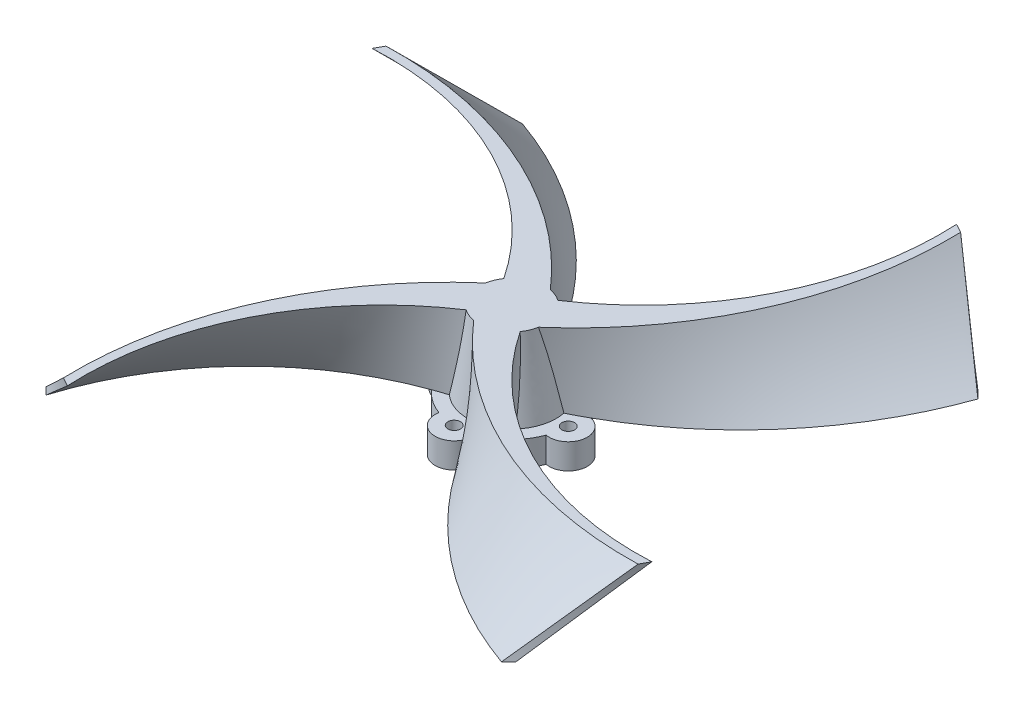
SolidWorks part; units mm, degrees
ref_plane "Front Plane" through (0, 0, 0) normal (0, 0, 1) x (1, 0, 0)
ref_plane "Top Plane" through (0, 0, 0) normal (0, 1, 0) x (1, 0, 0)
ref_plane "Right Plane" through (0, 0, 0) normal (1, 0, 0) x (0, 0, -1)
sketch "Sketch1" plane through (0, 0, 0) normal (0, 1, 0) x (1, 0, 0)
  circle A0 centre (0, 0) radius 22.5
  circle A1 centre (-22.4978, 0.3133) radius 2.5
  circle A2 centre (-22.4978, 0.3133) radius 7.5
  circle A3 centre (0.3133, 22.4978) radius 7.5
  circle A4 centre (0.3133, 22.4978) radius 2.5
  circle A5 centre (22.4978, -0.3133) radius 7.5
  circle A6 centre (22.4978, -0.3133) radius 2.5
  circle A7 centre (-0.3133, -22.4978) radius 7.5
  circle A8 centre (-0.3133, -22.4978) radius 2.5
  point P18 (0, 0)
  point P23 (0, 0)
  dimension "D1" = 45
  dimension "D2" = 15
  dimension "D3" = 5
  dimension "D5" = 4
  dimension "D6" = 22.4978
  dimension "D7" = 31.8198
  dimension "D4" = 22.4978
extrude "Boss-Extrude1" add sketch "Sketch1" along normal blind 10 contours A7 A0 A5 A3 A2 | A4 A0 A3 | A4 A0 A3 | A6 A0 A5 | A6 A0 A5 | A8 A0 A7 | A8 A0 A7 | A0 A2 A1 | A0 A2 A1 region at (18.7951, 0, 0.2617) region at (25.672, 0, 0.3574) region at (0, 0, 0) region at (0.2617, 0, -18.7951) region at (0.3574, 0, -25.672) region at (-0.3574, 0, 25.672) region at (-0.2617, 0, 18.7951) region at (-18.7951, 0, -0.2617) region at (-25.672, 0, -0.3574)
ref_plane "Plane1" through (0, 40, 0) normal (0, 1, 0) x (1, 0, 0)
sketch "Sketch11" plane through (0, 10, 0) normal (0, 1, 0) x (1, 0, 0)
  arc A1 (93.9749, 89.826) -> (91.1669, 92.6747) centre (0, 0) ccw
  arc A2 (12.4531, 1.0822) -> (93.9749, 89.826) centre (-50.7027, 140.9141) ccw
  arc A3 (5.4403, 11.254) -> (91.1669, 92.6747) centre (-24.3394, 128.4491) ccw
  arc A4 (12.4531, 1.0822) -> (5.4403, 11.254) centre (0, 0) ccw
  dimension "D1" = 11.254
  dimension "D2" = 260
  dimension "D3" = 120.9194
  dimension "D4" = 153.4327
  dimension "D7" = 25
  dimension "D5" = 12.4531
  dimension "D6" = 93.9749
  dimension "D8" = 4
sketch "Sketch13" plane through (0, 40, 0) normal (0, 1, 0) x (1, 0, 0)
  arc A1 (63.627, 113.3649) -> (60.1092, 115.2688) centre (0, 0) ccw
  arc A2 (60.1092, 115.2688) -> (6.9761, 10.3722) centre (-57.8825, 109.1299) cw
  arc A3 (63.627, 113.3649) -> (12.1677, -2.863) centre (-83.8031, 109.1332) cw
  arc A4 (12.1677, -2.863) -> (6.9761, 10.3722) centre (0, 0) ccw
  dimension "D1" = 6.9761
  dimension "D4" = 118.1513
  dimension "D7" = 147.4908
  dimension "D8" = 25
  dimension "D2" = 4
  dimension "D3" = 12.1677
  dimension "D5" = 60.1092
loft "Loft1" add profiles "Sketch13", "Sketch11" connector at (63.627, 40, -113.3649) connector at (93.9749, 10, -89.826)
pattern_circular "CirPattern2" count 4 over 360 about axis through (0, 40, 0) along (0, -1, 0) of "Loft1"
sketch "Sketch15" plane through (0, 10, 0) normal (0, 1, 0) x (1, 0, 0)
  circle A0 centre (0, 0) radius 17.5
  dimension "D1" = 35
sketch "Sketch16" plane through (0, 40, 0) normal (0, 1, 0) x (1, 0, 0)
  circle A0 centre (0, 0) radius 13
  dimension "D1" = 26
loft "Loft3" add profiles "Sketch16", "Sketch15" connector at (-4.869, 40, 12.0537) connector at (-0.6266, 10, 17.4888)
